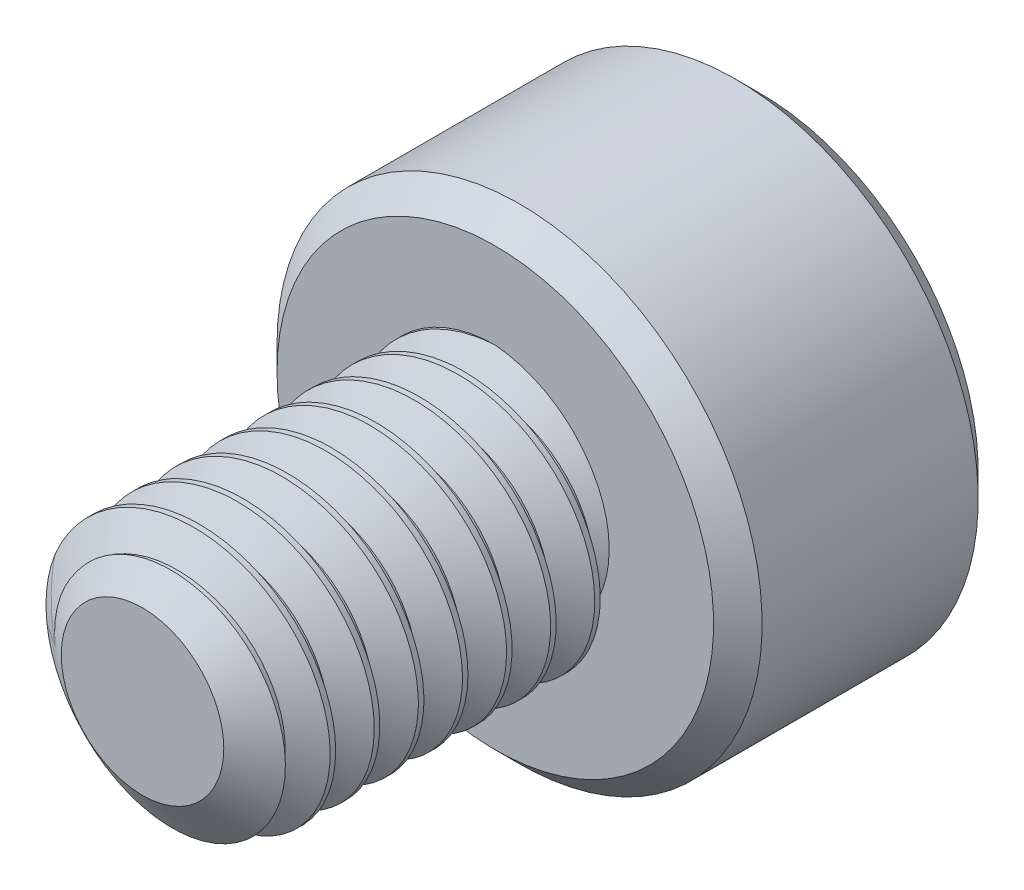
SolidWorks part; units mm, degrees
ref_plane "Front Plane" through (0, 0, 0) normal (0, 0, 1) x (1, 0, 0)
ref_plane "Top Plane" through (0, 0, 0) normal (0, 1, 0) x (1, 0, 0)
ref_plane "Right Plane" through (0, 0, 0) normal (1, 0, 0) x (0, 0, -1)
sketch "Sketch1" plane through (0, 0, 0) normal (0, 0, 1) x (1, 0, 0)
  circle A0 centre (0, 0) radius 1.5
  dimension "OD" = 3
extrude "Extrude1" add sketch "Sketch1" against normal blind 4
sketch "Sketch2" plane through (0, 0, 0) normal (0, 0, 1) x (1, 0, 0)
  circle A0 centre (0, 0) radius 1.5 construction
  circle A1 centre (0, 0) radius 1.5
curve "Helix/Spiral1" pitch 0.5 height 4.5 radius 1.5 centre (0, 0, 0) axis (0, 0, -1) start towards (0, 1, 0) parameters "pitch"=0.5
sketch "Sketch3" plane through (0, 0, 0) normal (1, 0, 0) x (0, 0, -1)
  line L0 (-0.4375, 1.5) -> (-0.25, 1.1752)
  line L1 (-0.25, 1.1752) -> (-0.1875, 1.1752)
  line L2 (-0.1875, 1.1752) -> (0, 1.5)
  line L3 (-0.4375, 1.5) -> (0, 1.5)
  line L4 (-0.2187, 1.5) -> (-0.2187, 1.1752) construction
  line L5 (-0.3437, 1.3376) -> (-0.0937, 1.3376) construction
  line L6 (0, 1.5) -> (0, -1.5) construction
  dimension "D1" = 0.0625
  dimension "D2" = 0.25
  dimension "D3" = 60
sweep "Cut-Sweep1" cut profiles "Sketch3" path "Helix/Spiral1"
sketch "Sketch4" plane through (0, 0, 0) normal (1, 0, 0) x (0, 0, -1)
  line L0 (0.4053, 1.5) -> (0, 0.9212)
  line L1 (0, 0.9212) -> (0, 1.5)
  line L2 (0.4053, 1.5) -> (0, 1.5)
  line L3 (-0.4375, 1.5) -> (0, 1.5) construction
  line L4 (0, 0) -> (7.0209, 0) construction
  dimension "D1" = 55
  dimension "D2" = 0.254
revolve "Cut-Revolve1" cut sketch "Sketch4" angle 360 about L4
sketch "Sketch5" plane through (0, 0, 0) normal (1, 0, 0) x (0, 0, -1)
  line L0 (4, -1.1822) -> (4, 1.0703) construction
  line L1 (4, 1.627) -> (87.4327, 1.627)
  line L2 (4, 1.627) -> (4, 0)
  line L3 (4, 0) -> (87.3125, 0)
  line L4 (87.3125, 1.2968) -> (87.3125, 0)
  line L5 (87.4327, 1.627) -> (87.3125, 1.2968)
  line L6 (0, 0) -> (9.9695, 0) construction
  point P3 (87.3125, 1.627)
  point P10 (87.3125, 1.627)
  dimension "D1" = 0.3302
  dimension "Thread min" = 87.3125
  dimension "D2" = 0.127
  dimension "D3" = 20
revolve "partially thread" [suppressed] add sketch "Sketch5" angle 360 about L6
sketch "Sketch6" plane through (0, 0, -4) normal (0, 0, -1) x (-1, 0, 0)
  circle A0 centre (0, 0) radius 2.75
  dimension "head dia" = 5.5
extrude "Extrude2" add sketch "Sketch6" along normal blind 3
sketch "Sketch7" plane through (0, 0, -7) normal (0, 0, -1) x (-1, 0, 0)
  line L1 (0, 1.4434) -> (-1.25, 0.7217)
  line L2 (-1.25, 0.7217) -> (-1.25, -0.7217)
  line L3 (-1.25, -0.7217) -> (0, -1.4434)
  line L4 (0, -1.4434) -> (1.25, -0.7217)
  line L5 (1.25, -0.7217) -> (1.25, 0.7217)
  line L6 (1.25, 0.7217) -> (0, 1.4434)
  circle A0 centre (0, 0) radius 1.25 construction
  dimension "hex dia" = 2.5
extrude "Cut-Extrude1" cut sketch "Sketch7" against normal blind 1.875
sketch "Sketch8" plane through (0, 0, -7) normal (0, 0, -1) x (-1, 0, 0)
  circle A0 centre (0, 0) radius 1.4434
extrude "Cut-Extrude2" cut sketch "Sketch8" against normal through all draft 45
chamfer "Chamfer1" distance 0.275 angle 45 2 edges at (-2.75, 0, -7) (-2.75, 0, -4)
sketch "Sketch9" plane through (0, 0, 0) normal (1, 0, 0) x (0, 0, -1)
  line L0 (0, 1.5) -> (0, -1.5) construction
  line L1 (2.75, 1.5) -> (2.75, -1.5) construction
  dimension "D1" = 2.75
equation "\"D3@Helix/Spiral1\" = \"screw length@Extrude1\"+\"pitch@Helix/Spiral1\""
equation "\"D1@Sketch3\" = \"pitch@Helix/Spiral1\"*.125"
equation "\"D2@Sketch3\" = \"pitch@Helix/Spiral1\"*.5"
equation "\"D1@Cut-Extrude1\" = \"hex dia@Sketch7\"*.75"
equation "\"D1@Chamfer1\" = \"head dia@Sketch6\"*.05"
equation "\"D1@Sketch9\" = \"pitch@Helix/Spiral1\"*5.5"
